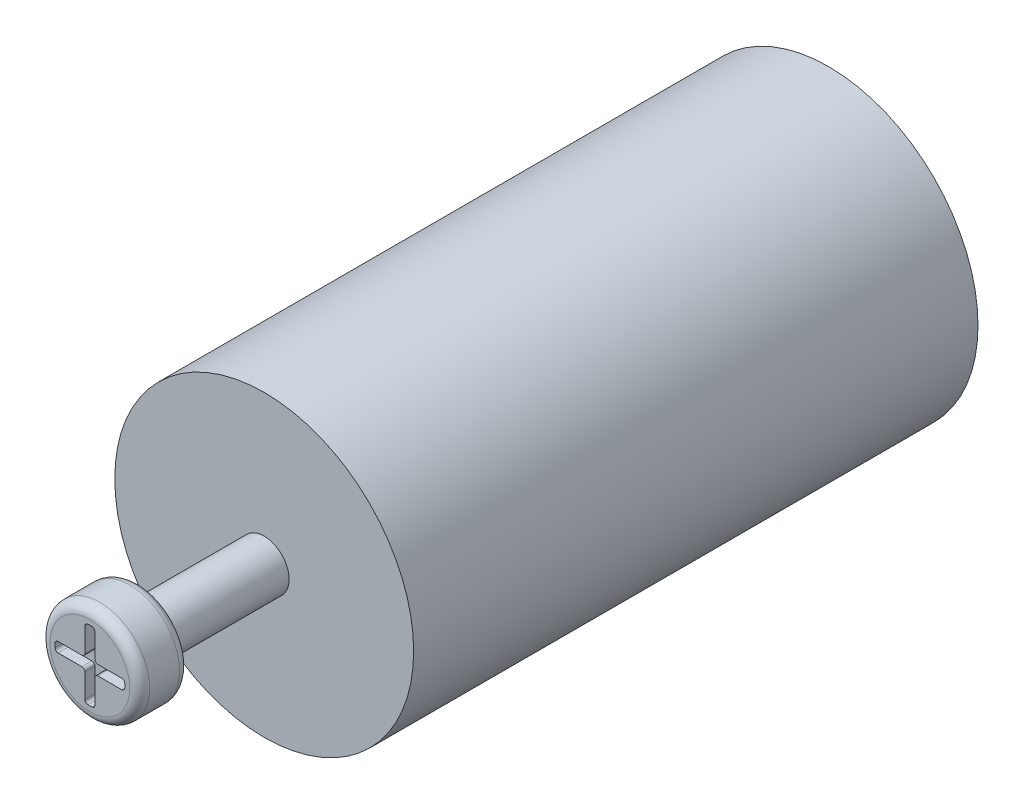
SolidWorks part; units mm, degrees
ref_plane "Front Plane" through (0, 0, 0) normal (0, 0, 1) x (1, 0, 0)
ref_plane "Top Plane" through (0, 0, 0) normal (0, 1, 0) x (1, 0, 0)
ref_plane "Right Plane" through (0, 0, 0) normal (1, 0, 0) x (0, 0, -1)
sketch "Sketch1" plane through (0, 0, 0) normal (0, 0, 1) x (1, 0, 0)
  circle A0 centre (0, 0) radius 3.175
extrude "Boss-Extrude1" add sketch "Sketch1" along normal blind 14.478
sketch "Sketch2" plane through (0, 0, 14.478) normal (0, 0, 1) x (1, 0, 0)
  circle A0 centre (0, 0) radius 38.1
extrude "Boss-Extrude2" add sketch "Sketch2" along normal blind 143.891
sketch "Sketch3" plane through (0, 0, 0) normal (0, 0, -1) x (-1, 0, 0)
  line L1 (-1.27, 5.715) -> (1.27, 5.715)
  line L2 (-1.27, 5.715) -> (-1.27, 0.635)
  line L3 (-1.27, 0.635) -> (1.27, 0.635)
  line L4 (1.27, 5.715) -> (1.27, 0.635)
  line L5 (-1.27, 5.715) -> (1.27, 0.635) construction
  line L6 (-1.27, 0.635) -> (1.27, 5.715) construction
  circle A0 centre (0, 0) radius 3.175 construction
  circle A1 centre (0, 0) radius 3.175 construction
  point P0 (0, 3.175)
extrude "Boss-Extrude3" add sketch "Sketch3" against normal up to surface (14.478 mm away) up to face at (3.175, 0, 14.478)
sketch "Sketch4" plane through (0, 0, 0) normal (0, 0, -1) x (-1, 0, 0)
  circle A0 centre (0, 0) radius 5.9995
extrude "Boss-Extrude4" add sketch "Sketch4" along normal blind 5.08
sketch "Sketch5" plane through (0, 0, 158.369) normal (0, 0, 1) x (1, 0, 0)
  circle A0 centre (0, 0) radius 6.35
extrude "Boss-Extrude5" add sketch "Sketch5" along normal blind 31.75
sketch "Sketch6" plane through (0, 0, 190.119) normal (0, 0, 1) x (1, 0, 0)
  circle A0 centre (0, 0) radius 12.7
extrude "Boss-Extrude6" add sketch "Sketch6" along normal blind 12.7
fillet "Fillet1" radius 2.54 2 edges at (12.7, 0, 190.119) (12.7, 0, 202.819)
sketch "Sketch7" plane through (0, 0, 202.819) normal (0, 0, 1) x (1, 0, 0)
  line L1 (-0.508, 8.89) -> (0.508, 8.89)
  line L2 (-1.27, 8.128) -> (-1.27, 2.032)
  line L3 (-0.508, -8.89) -> (0.508, -8.89)
  line L4 (1.27, 8.128) -> (1.27, 2.032)
  line L7 (-8.128, 1.27) -> (-2.032, 1.27)
  line L8 (-8.89, 0.508) -> (-8.89, -0.508)
  line L9 (-8.128, -1.27) -> (-2.032, -1.27)
  line L10 (8.89, 0.508) -> (8.89, -0.508)
  line L16 (2.032, -1.27) -> (8.128, -1.27)
  line L17 (1.27, -2.032) -> (1.27, -8.128)
  line L21 (-1.27, -2.032) -> (-1.27, -8.128)
  line L22 (2.032, 1.27) -> (8.128, 1.27)
  arc A0 (0.508, 8.89) -> (1.27, 8.128) centre (0.508, 8.128) cw
  arc A1 (-1.27, 8.128) -> (-0.508, 8.89) centre (-0.508, 8.128) cw
  arc A2 (-2.032, 1.27) -> (-1.27, 2.032) centre (-2.032, 2.032) ccw
  arc A3 (2.032, 1.27) -> (1.27, 2.032) centre (2.032, 2.032) cw
  arc A4 (8.128, 1.27) -> (8.89, 0.508) centre (8.128, 0.508) cw
  arc A5 (8.128, -1.27) -> (8.89, -0.508) centre (8.128, -0.508) ccw
  arc A6 (2.032, -1.27) -> (1.27, -2.032) centre (2.032, -2.032) ccw
  arc A7 (0.508, -8.89) -> (1.27, -8.128) centre (0.508, -8.128) ccw
  arc A8 (-1.27, -8.128) -> (-0.508, -8.89) centre (-0.508, -8.128) ccw
  arc A9 (-2.032, -1.27) -> (-1.27, -2.032) centre (-2.032, -2.032) cw
  arc A10 (-8.89, -0.508) -> (-8.128, -1.27) centre (-8.128, -0.508) ccw
  arc A11 (-8.89, 0.508) -> (-8.128, 1.27) centre (-8.128, 0.508) cw
  point P0 (0, 0)
  point P6 (0, 0)
  point P29 (1.27, -1.27)
  point P36 (-1.27, -1.27)
  dimension "D1" = 0.762
extrude "Cut-Extrude1" cut sketch "Sketch7" against normal blind 2.54
